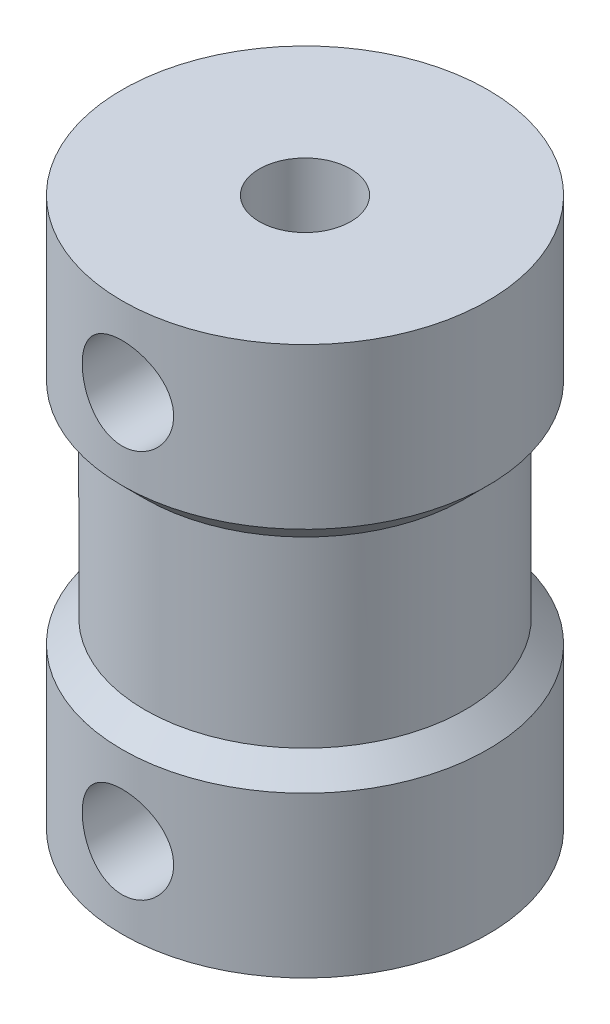
SolidWorks part; units mm, degrees
ref_plane "Front Plane" through (0, 0, 0) normal (0, 0, 1) x (1, 0, 0)
ref_plane "Top Plane" through (0, 0, 0) normal (0, 1, 0) x (1, 0, 0)
ref_plane "Right Plane" through (0, 0, 0) normal (1, 0, 0) x (0, 0, -1)
sketch "Sketch1" plane through (0, 0, 0) normal (0, 1, 0) x (1, 0, 0)
  circle A0 centre (0, 0) radius 4
  circle A1 centre (0, 0) radius 1
  dimension "D1" = 8
  dimension "D2" = 2
extrude "Boss-Extrude1" add sketch "Sketch1" along normal mid plane 12
sketch "Sketch2" plane through (0, 0, 0) normal (0, 1, 0) x (1, 0, 0)
  circle A0 centre (0, 0) radius 10.0668
  circle A1 centre (0, 0) radius 3.5
  dimension "D1" = 7
extrude "Cut-Extrude1" cut sketch "Sketch2" against normal mid plane 6
chamfer "Chamfer1" distance 1 angle 45 2 edges at (0, -3, 3.5) (0, 3, 3.5)
sketch "Sketch3" plane through (0, 0, 0) normal (0, 0, 1) x (1, 0, 0)
  circle A0 centre (0, 4.25) radius 1
  circle A1 centre (0, -4.25) radius 1
  dimension "D1" = 2
extrude "Cut-Extrude2" cut sketch "Sketch3" along normal through all
